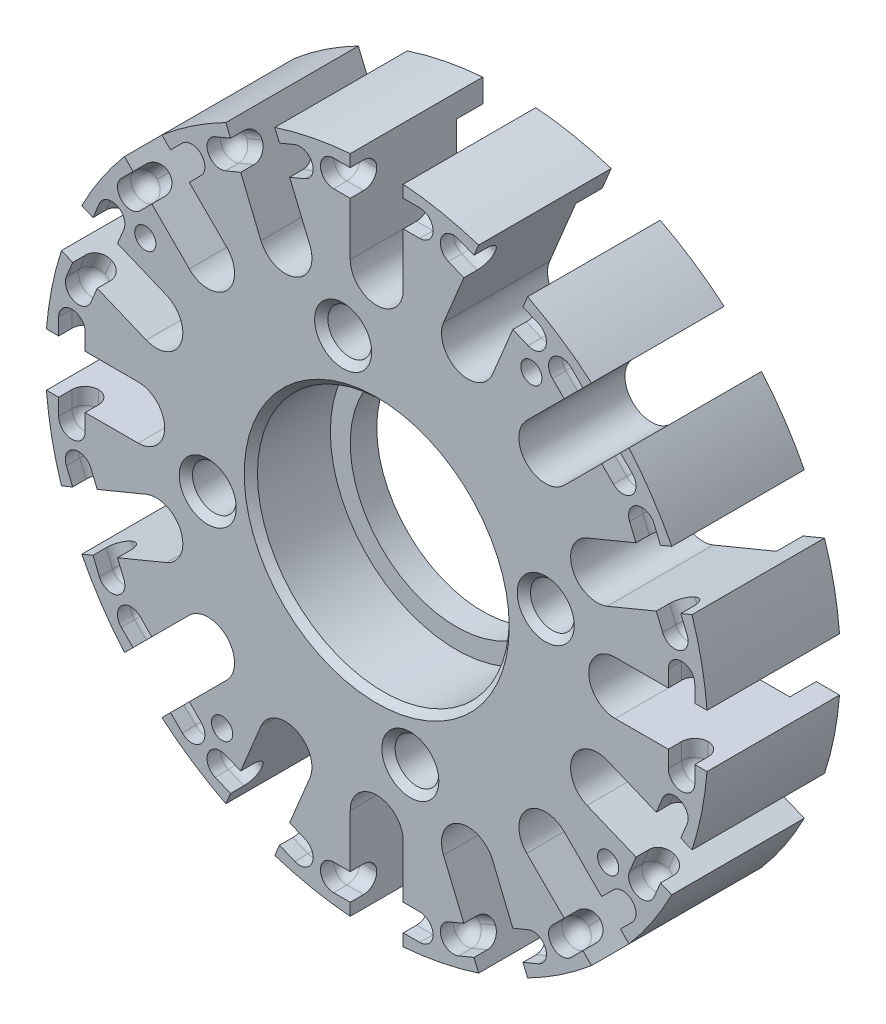
SolidWorks part; units mm, degrees
material "白色 POM"
ref_plane "前视基准面" through (0, 0, 0) normal (0, 0, 1) x (1, 0, 0)
ref_plane "上视基准面" through (0, 0, 0) normal (0, 1, 0) x (1, 0, 0)
ref_plane "右视基准面" through (0, 0, 0) normal (1, 0, 0) x (0, 0, -1)
sketch "草图1" plane through (0, 0, 0) normal (0, 0, 1) x (1, 0, 0)
  circle A0 centre (0, 0) radius 25
  dimension "D1" = 50
extrude "拉伸1" add sketch "草图1" along normal blind 10
sketch "草图10" plane through (0, 0, 10) normal (0, 0, 1) x (1, 0, 0)
  circle A0 centre (0, 0) radius 8
  dimension "D1" = 16
extrude "拉伸7" cut sketch "草图10" against normal up to surface (10 mm away) up to face at (25, 0, 0)
sketch "草图6" plane through (0, 0, 0) normal (0, 0, -1) x (-1, 0, 0)
  circle A0 centre (0, 0) radius 23.25
  dimension "D1" = 46.5
extrude "拉伸6" cut sketch "草图6" against normal blind 2
sketch "草图2" plane through (0, 0, 10) normal (0, 0, 1) x (1, 0, 0)
  circle A0 centre (0, 0) radius 9.5
  dimension "D1" = 19
extrude "拉伸2" cut sketch "草图2" against normal blind 6
sketch "草图3" plane through (0, 0, 10) normal (0, 0, 1) x (1, 0, 0)
  line L0 (0, 0) -> (0, 13) construction
  line L1 (0, 0) -> (-2.5362, 12.7502) construction
  circle A0 centre (0, 0) radius 13 construction
  circle A1 centre (-2.5362, 12.7502) radius 1.65
  dimension "D1" = 26
  dimension "D2" = 3.3
  dimension "D3" = 11.25
extrude "拉伸3" cut sketch "草图3" against normal blind 10
cosmetic thread "装饰螺纹线1" parameters "D2"=4
pattern_circular "阵列(圆周)1" count 4 over 360 about axis through (0, 0, 0) along (0, 0, 1) of "拉伸3"
cosmetic thread "装饰螺纹线2" parameters "D2"=4
cosmetic thread "装饰螺纹线3" parameters "D2"=4
cosmetic thread "装饰螺纹线4" parameters "D2"=4
sketch "草图4" plane through (0, 0, 10) normal (0, 0, 1) x (1, 0, 0)
  circle A0 centre (0, 0) radius 20 construction
  circle A1 centre (0, 20) radius 0.625
  dimension "D1" = 40
  dimension "D2" = 1.25
extrude "拉伸4" [suppressed] cut sketch "草图4" against normal blind 10
cosmetic thread "装饰螺纹线5" [suppressed] parameters "D2"=1.6
pattern_circular "阵列(圆周)2" [suppressed] count 6 every 60
sketch "草图5" plane through (0, 0, 10) normal (0, 0, 1) x (1, 0, 0)
  line L0 (-18, 2) -> (-24.9199, 2)
  line L1 (-18, -2) -> (-24.9199, -2)
  circle A0 centre (0, 0) radius 18 construction
  arc A1 (-18, -2) -> (-18, 2) centre (-18, 0) ccw
  arc A2 (-24.9199, 2) -> (-24.9199, -2) centre (0, 0) ccw
  circle A3 centre (0, 0) radius 25 construction
  dimension "D1" = 36
  dimension "D2" = 4
extrude "拉伸5" cut sketch "草图5" against normal blind 10
pattern_circular "阵列(圆周)3" count 16 over 360 about axis through (0, 0, 0) along (0, 0, 1) of "拉伸5"
sketch "草图8" plane through (0, 0, 10) normal (0, 0, 1) x (1, 0, 0)
  circle A0 centre (0, 0) radius 23
  dimension "D1" = 46
sketch "草图9" [suppressed] plane through (0, 0, 0) normal (1, 0, 0) x (0, 0, -1)
  line L0 (-8.5, -24) -> (-9.5, -24)
  line L1 (-9.5, -24) -> (-9.5, -22)
  line L2 (-8.5, -22) -> (-9.5, -22)
  line L3 (-9.5, 9.5) -> (-9.5, -9.5) construction
  line L4 (0, 0) -> (-9.5, 0) construction
  line L5 (-9.5, 9.1187) -> (-9.5, 5.271) construction
  arc A0 (-8.5, -24) -> (-8.5, -22) centre (-8.5, -23) ccw
  dimension "D1" = 1
  dimension "D4" = 23
  dimension "D2" = 1
  dimension "D3" = 1
sweep "切除-扫描1" [suppressed] cut profiles "草图9" path "草图8"
chamfer "倒角1" distance 0.5 angle 45 5 edges at (12.7502, 0.8862, 10) (0.8862, -12.7502, 10) (-12.7502, -0.8862, 10) (-0.8862, 12.7502, 10) (9.5, 0, 10)
chamfer "倒角2" [suppressed] distance 0.25 angle 45
sketch "草图11" plane through (0, 0, 10) normal (0, 0, 1) x (1, 0, 0)
  line L0 (-22.5, 3.75) -> (-22.5, -3.75) construction
  line L1 (-23.5, 3.75) -> (-21.5, 3.75) construction
  line L2 (-23.5, 3.75) -> (-23.5, -3.75)
  line L3 (-23.5, -3.75) -> (-21.5, -3.75)
  line L4 (-21.5, 3.75) -> (-21.5, -3.75)
  line L5 (-22.5, 0) -> (0, 0) construction
  line L6 (-20.8002, 11.5613) -> (-23.3654, 4.5136)
  line L7 (-23.3654, 4.5136) -> (-21.486, 3.8296) construction
  line L8 (-21.486, 3.8296) -> (-18.9208, 10.8773)
  line L9 (-18.9208, 10.8773) -> (-20.8002, 11.5613)
  line L10 (-19.8605, 11.2193) -> (-22.4257, 4.1716) construction
  line L11 (0, 0) -> (-21.1431, 7.6955) construction
  arc A0 (-21.486, 3.8296) -> (-21.5, 3.75) centre (0, 0) ccw
  arc A1 (-23.3654, 4.5136) -> (-23.5, 3.75) centre (0, 0) ccw
  arc A2 (-23.7883, 7.6887) -> (-24.9199, 2) centre (0, 0) ccw construction
  arc A3 (-22.4257, 4.1716) -> (-22.5, 3.75) centre (0, 0) ccw construction
  dimension "D1" = 7.5
  dimension "D2" = 2
  dimension "D3" = 22.5
  dimension "D4" = 20
sketch "草图12" [suppressed] plane through (0, 0, 9.5) normal (0, 0, 1) x (1, 0, 0)
  line L1 (-20.3304, 11.3903) -> (-22.8955, 4.3426) construction
  line L3 (-22.3654, 5.7991) -> (-22.8955, 4.3426)
  line L5 (-23, 3.75) -> (-23, -3.75) construction
  line L7 (-23, 3.75) -> (-23, 0)
  line L9 (-24.1536, 6.45) -> (-18.6066, 4.4311) construction
  line L11 (-24.1536, 6.45) -> (-18.6066, 4.4311) construction
  line L13 (0, 0) -> (-24.5802, 0) construction
  arc A1 (-22.8955, 4.3426) -> (-23, 3.75) centre (0, 0) ccw construction
  arc A3 (-22.8955, 4.3426) -> (-23, 3.75) centre (0, 0) ccw
sketch "草图13" [suppressed] plane through (0, 0, 0) normal (0, 1, 0) x (1, 0, 0)
  line L0 (0, -9.5) -> (-24.5802, -9.5) construction
  line L1 (-24, -9.5) -> (-22, -9.5)
  line L2 (-24, -9.5) -> (-24, -7.5)
  line L3 (-24, -7.5) -> (-22, -7.5)
  line L4 (-22, -9.5) -> (-22, -7.5)
  line L5 (-23, -7.5) -> (-23, -9.5) construction
  dimension "D1" = 2
  dimension "D2" = 2
sweep "切除-扫描2" [suppressed] cut profiles "草图13" path "草图12"
sketch "草图15" plane through (0, 0, 10) normal (0, 0, 1) x (1, 0, 0)
  line L0 (-23, 4.25) -> (-23, -4.25) construction
  line L2 (-24, 3.25) -> (-24, -3.25)
  line L4 (-22, 3.25) -> (-22, -3.25)
  line L5 (-23, 0) -> (0, 0) construction
  arc A0 (-24, -3.25) -> (-22, -3.25) centre (-23, -3.25) ccw
  arc A1 (-22, 3.25) -> (-24, 3.25) centre (-23, 3.25) ccw
  dimension "D1" = 23
  dimension "D2" = 2
  dimension "D3" = 8.5
extrude "拉伸10" cut sketch "草图15" against normal blind 2
fillet "圆角2" [suppressed] radius 1
fillet "圆角3" radius 1 6 edges at (-22, -2.625, 8) (-22, 2.625, 8) (-24, -2.625, 8) (-24, 2.625, 8) (-23, -4.25, 8) (-23, 4.25, 8)
pattern_circular "阵列(圆周)6" count 16 over 360 about axis through (0, 0, 0) along (0, 0, 1) of "拉伸10"
sketch "草图17" plane through (0, 0, 2) normal (0, 0, -1) x (-1, 0, 0)
  line L0 (0, 0) -> (-11.667, 17.4609) construction
  line L1 (0, 0) -> (2.5362, 12.7502) construction
  circle A0 centre (0, 0) radius 21 construction
  dimension "D1" = 42
  dimension "D2" = 45
hole_wizard "M2 螺纹孔1" positions "3D草图1" profile "草图18" tap size "M2" standard "GB" end condition through all
sketch3d "3D草图1"
  point P0 (11.667, 17.4609, 2)
cosmetic thread "孔螺蚊线1" parameters "D2"=2
sketch "草图18" plane through (11.667, 17.4609, 2) normal (1, 0, 0) x (0, 1, 0)
  line L0 (0, 0) -> (0, 8)
  line L1 (0, 8) -> (0.8, 8)
  line L2 (0.8, 8) -> (0.8, 0)
  line L5 (0.8, 0) -> (0, 0)
  line L11 (0, -6.35) -> (0, 107.95) construction
  dimension "通孔螺纹孔钻头直径" = 1.6
  dimension "通孔螺纹孔钻头深度" = 8
pattern_circular "阵列(圆周)7" count 4 over 360 about axis through (0, 0, 0) along (0, 0, 1) of "M2 螺纹孔1"
chamfer "倒角3" distance 0.25 angle 15 4 edges at (-18.2609, 11.667, 2) (-12.467, -17.4609, 2) (16.6609, -11.667, 2) (10.867, 17.4609, 2) first distance on face at (16.6609, -11.667, 2)
fillet "圆角5" radius 1 12 edges at (-17.4125, -13.7002, 8) (-18.8267, -15.1144, 8) (-15.1144, -18.8267, 8) (-13.7002, -17.4125, 8) (-21.1686, -11.6096, 8) (-19.3208, -10.8442, 8) (-21.3299, -5.9939, 8) (-23.1777, -6.7592, 8) (-19.2687, -13.2583, 8) (-13.2583, -19.2687, 8) (-19.6228, -12.7282, 8) (-22.8756, -4.8752, 8)
fillet "圆角6" radius 1 78 edges at (-23.1777, 6.7592, 8) (-21.3299, 5.9939, 8) (-19.3208, 10.8442, 8) (-21.1686, 11.6096, 8) (-18.8267, 15.1144, 8) (-17.4125, 13.7002, 8) (-13.7002, 17.4125, 8) (-15.1144, 18.8267, 8) (-11.6096, 21.1686, 8) (-10.8442, 19.3208, 8) (-5.9939, 21.3299, 8) (-6.7592, 23.1777, 8) (-2.625, 24, 8) (-2.625, 22, 8) (2.625, 22, 8) (2.625, 24, 8) (6.7592, 23.1777, 8) (5.9939, 21.3299, 8) (10.8442, 19.3208, 8) (11.6096, 21.1686, 8) (15.1144, 18.8267, 8) (13.7002, 17.4125, 8) (17.4125, 13.7002, 8) (18.8267, 15.1144, 8) (21.1686, 11.6096, 8) (19.3208, 10.8442, 8) (21.3299, 5.9939, 8) (23.1777, 6.7592, 8) (24, 2.625, 8) (22, 2.625, 8) (22, -2.625, 8) (24, -2.625, 8) (23.1777, -6.7592, 8) (21.3299, -5.9939, 8) (19.3208, -10.8442, 8) (21.1686, -11.6096, 8) (18.8267, -15.1144, 8) (17.4125, -13.7002, 8) (13.7002, -17.4125, 8) (15.1144, -18.8267, 8) (11.6096, -21.1686, 8) (10.8442, -19.3208, 8) (5.9939, -21.3299, 8) (6.7592, -23.1777, 8) (2.625, -24, 8) (2.625, -22, 8) (-2.625, -22, 8) (-2.625, -24, 8) (-6.7592, -23.1777, 8) (-5.9939, -21.3299, 8) (-10.8442, -19.3208, 8) (-11.6096, -21.1686, 8) (-22.8756, 4.8752, 8) (-19.6228, 12.7282, 8) (-19.2687, 13.2583, 8) (-13.2583, 19.2687, 8) (-12.7282, 19.6228, 8) (-4.8752, 22.8756, 8) (-4.25, 23, 8) (4.25, 23, 8) (4.8752, 22.8756, 8) (12.7282, 19.6228, 8) (13.2583, 19.2687, 8) (19.2687, 13.2583, 8) (19.6228, 12.7282, 8) (22.8756, 4.8752, 8) (23, 4.25, 8) (23, -4.25, 8) (22.8756, -4.8752, 8) (19.6228, -12.7282, 8) (19.2687, -13.2583, 8) (13.2583, -19.2687, 8) (12.7282, -19.6228, 8) (4.8752, -22.8756, 8) (4.25, -23, 8) (-4.25, -23, 8) (-4.8752, -22.8756, 8) (-12.7282, -19.6228, 8)
